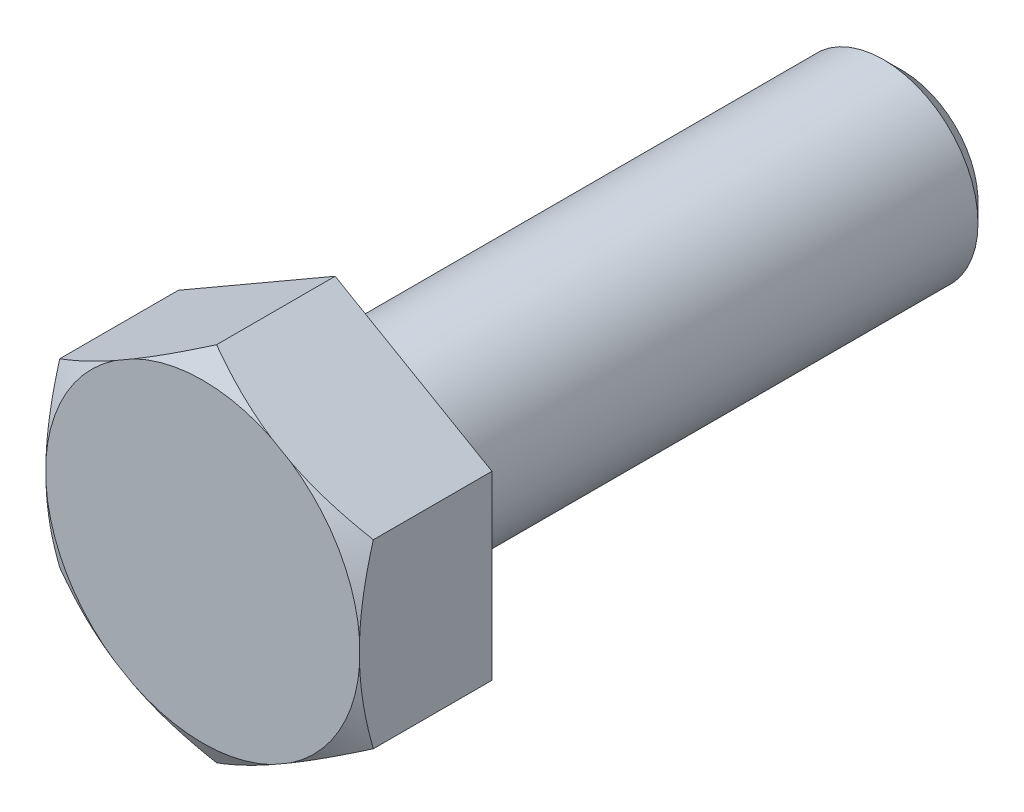
SolidWorks part; units mm, degrees
material "Простая углеродистая сталь"
ref_plane "Спереди" through (0, 0, 0) normal (0, 0, 1) x (1, 0, 0)
ref_plane "Сверху" through (0, 0, 0) normal (0, 1, 0) x (1, 0, 0)
ref_plane "Справа" through (0, 0, 0) normal (1, 0, 0) x (0, 0, -1)
sketch "Эскиз1" plane through (0, 0, 0) normal (0, 1, 0) x (1, 0, 0)
  line L0 (0, 0) -> (-4, 0)
  line L1 (-4, 0) -> (-4, 2.8)
  line L2 (-4, 2.8) -> (-2, 2.8)
  line L3 (-2, 2.8) -> (-2, 14.8)
  line L4 (-2, 14.8) -> (0, 14.8)
  line L5 (0, 14.8) -> (0, 0)
  dimension "D1" = 4
  dimension "D2" = 2.8
  dimension "D3" = 12
  dimension "D4" = 2
revolve "Повернуть1" add sketch "Эскиз1" angle 360 about L5
sketch "Эскиз2" plane through (0, 0, 0) normal (0, 0, 1) x (1, 0, 0)
  line L1 (0, 3.83) -> (-3.3169, 1.915)
  line L2 (-3.3169, 1.915) -> (-3.3169, -1.915)
  line L3 (-3.3169, -1.915) -> (0, -3.83)
  line L4 (0, -3.83) -> (3.3169, -1.915)
  line L5 (3.3169, -1.915) -> (3.3169, 1.915)
  line L6 (3.3169, 1.915) -> (0, 3.83)
  circle A0 centre (0, 0) radius 3.3169 construction
  dimension "D1" = 7.66
extrude "Вырез-Вытянуть1" cut sketch "Эскиз2" against normal up to surface (2.8 mm away) flip side to cut up to face at (-4, 0, -2.8)
sketch "Эскиз3" plane through (0, 0, 0) normal (1, 0, 0) x (0, 0, -1)
  line L1 (0, 0) -> (-50000, 0) construction
  line L3 (0, 3.83) -> (0.2916, 3.83)
  line L5 (2.8, 3.83) -> (0, 3.83) construction
  line L12 (0.2916, 3.83) -> (0, 3.325)
  line L13 (0, 1.915) -> (0, 3.83) construction
  line L14 (0, 3.325) -> (0, 3.83)
  dimension "D1" = 30
  dimension "D2" = 3.325
revolve "Вырез-Повернуть1" cut sketch "Эскиз3" angle 360 about L1
chamfer "Фаска1" distance 0.4 angle 45 1 edges at (-2, 0, -14.8)
fillet "Скругление1" radius 0.4 1 edges at (-2, 0, -2.8)
